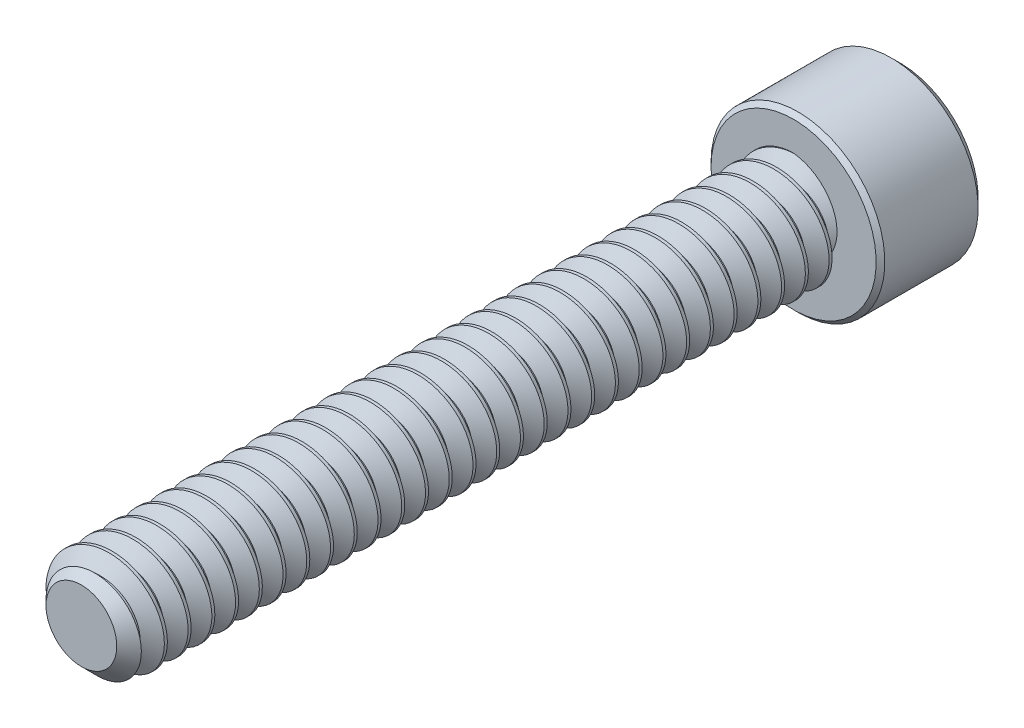
SolidWorks part; units mm, degrees
ref_plane "Front Plane" through (0, 0, 0) normal (0, 0, 1) x (1, 0, 0)
ref_plane "Top Plane" through (0, 0, 0) normal (0, 1, 0) x (1, 0, 0)
ref_plane "Right Plane" through (0, 0, 0) normal (1, 0, 0) x (0, 0, -1)
sketch "Sketch0" plane through (0, 0, 0) normal (1, 0, 0) x (0, 0, -1)
  line L0 (0, 0) -> (19.05, 0) construction
  point P2 (21.8948, 0)
  point P4 (0, 0)
  dimension "D1" = 19.05
  dimension "D2" = 2.8448
  dimension "Min Thread" = 0
sketch "Sketch1" plane through (0, 0, 0) normal (0, 0, 1) x (1, 0, 0)
  circle A0 centre (0, 0) radius 1.4224
  dimension "OD" = 2.8448
extrude "Extrude1" add sketch "Sketch1" against normal blind 19.05
sketch "Sketch2" plane through (0, 0, 0) normal (0, 0, 1) x (1, 0, 0)
  circle A0 centre (0, 0) radius 1.4224 construction
  circle A1 centre (0, 0) radius 1.4224
curve "Helix/Spiral1" pitch 0.635 height 19.685 turns 31 parameters "pitch"=0.635
chamfer "Chamfer3" distance 0.4763 angle 45 1 edges at (1.4224, 0, 0)
sketch "Sketch3" plane through (0, 0, 0) normal (1, 0, 0) x (0, 0, -1)
  line L0 (-0.5556, 1.4224) -> (-0.3175, 1.01)
  line L1 (-0.3175, 1.01) -> (-0.2381, 1.01)
  line L2 (-0.2381, 1.01) -> (0, 1.4224)
  line L3 (-0.5556, 1.4224) -> (0, 1.4224)
  line L4 (-0.2778, 1.4224) -> (-0.2778, 1.01) construction
  line L5 (-0.4366, 1.2162) -> (-0.1191, 1.2162) construction
  line L6 (0, 1.4224) -> (0, -1.4224) construction
  dimension "D1" = 0.0794
  dimension "D2" = 0.3175
  dimension "D3" = 60
sweep "Cut-Sweep1" cut profiles "Sketch3" path "Helix/Spiral1"
sketch "Sketch5" plane through (0, 0, 0) normal (1, 0, 0) x (0, 0, -1)
  line L0 (19.05, -1.0232) -> (19.05, 1.0149) construction
  line L1 (19.05, 1.4224) -> (0, 1.4224)
  line L2 (19.05, 1.4224) -> (19.05, 0)
  line L3 (19.05, 0) -> (-0.5177, 0)
  line L4 (0, 0) -> (19.05, 0) construction
  line L5 (0, 1.4224) -> (-0.5177, 0)
  line L6 (0, 0) -> (21.59, 0) construction
  dimension "D1" = 70
  dimension "D3" = 2.54
revolve "partially thread" [suppressed] add sketch "Sketch5" angle 360 about L6
sketch "Sketch6" plane through (0, 0, -19.05) normal (0, 0, -1) x (-1, 0, 0)
  circle A0 centre (0, 0) radius 2.3241
  dimension "head dia" = 4.6482
extrude "Extrude2" add sketch "Sketch6" along normal blind 2.8448
sketch "Sketch7" plane through (0, 0, -21.8948) normal (0, 0, -1) x (-1, 0, 0)
  line L1 (0, 1.3748) -> (-1.1906, 0.6874)
  line L2 (-1.1906, 0.6874) -> (-1.1906, -0.6874)
  line L3 (-1.1906, -0.6874) -> (0, -1.3748)
  line L4 (0, -1.3748) -> (1.1906, -0.6874)
  line L5 (1.1906, -0.6874) -> (1.1906, 0.6874)
  line L6 (1.1906, 0.6874) -> (0, 1.3748)
  circle A0 centre (0, 0) radius 1.1906 construction
  dimension "hex dia" = 2.3813
extrude "Cut-Extrude1" cut sketch "Sketch7" against normal blind 1.7859
sketch "Sketch8" plane through (0, 0, -21.8948) normal (0, 0, -1) x (-1, 0, 0)
  circle A0 centre (0, 0) radius 1.3748
extrude "Cut-Extrude2" cut sketch "Sketch8" against normal through all draft 45
chamfer "Chamfer1" distance 0.2324 angle 45 1 edges at (-2.3241, 0, -21.8948)
chamfer "Chamfer2" distance 0.1162 angle 45 1 edges at (-2.3241, 0, -19.05)
sketch "Sketch9" plane through (0, 0, 0) normal (1, 0, 0) x (0, 0, -1)
  line L0 (0, 1.4224) -> (0, -1.4224) construction
  line L1 (1.5875, 1.4224) -> (1.5875, -1.4224) construction
  line L2 (21.8948, 2.3241) -> (21.8948, -2.3241) construction
  line L3 (19.05, 2.3241) -> (19.05, -2.3241) construction
  line L4 (19.05, 2.2079) -> (19.05, -2.2079) construction
  line L5 (21.8948, -2.0917) -> (21.8948, 2.0917) construction
  line L6 (19.05, -2.3241) -> (19.05, 2.3241) construction
  line L7 (0, 0.9462) -> (0, -0.9462) construction
  line L8 (-0.5556, 1.4224) -> (0, 1.4224) construction
  line L9 (1.5875, 0) -> (0, 0) construction
  dimension "D1" = 1.5875
equation "\"D3@Helix/Spiral1\" = \"screw length@Extrude1\"+\"pitch@Helix/Spiral1\""
equation "\"D1@Sketch3\" = \"pitch@Helix/Spiral1\"*.125"
equation "\"D2@Sketch3\" = \"pitch@Helix/Spiral1\"*.5"
equation "\"D1@Cut-Extrude1\" = \"hex dia@Sketch7\"*.75"
equation "\"D1@Chamfer1\" = \"head dia@Sketch6\"*.05"
equation "\"D1@Sketch9\" = \"pitch@Helix/Spiral1\"*2.50"
equation "\"D1@Chamfer2\" = \"D1@Chamfer1\"/2"
equation "\"D1@Chamfer3\" = \"pitch@Helix/Spiral1\"*.750"
equation "\"D1@Sketch0\" = \"screw length@Extrude1\""
equation "\"D2@Sketch0\" = \"head depth@Extrude2\""
